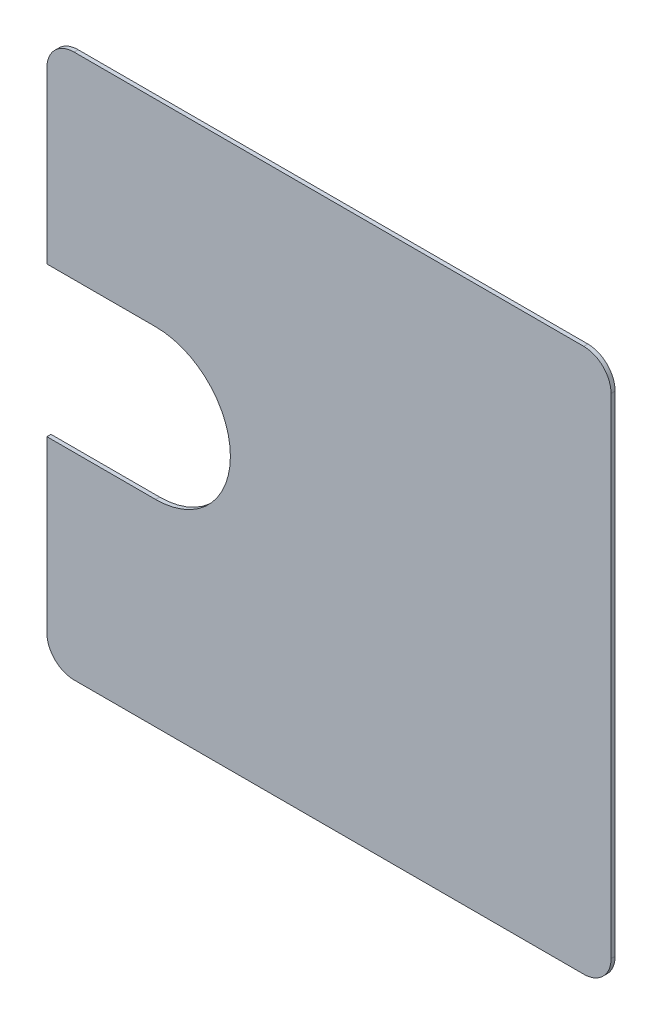
SolidWorks part; units mm, degrees
ref_plane "前视基准面" through (0, 0, 0) normal (0, 0, 1) x (1, 0, 0)
ref_plane "上视基准面" through (0, 0, 0) normal (0, 1, 0) x (1, 0, 0)
ref_plane "右视基准面" through (0, 0, 0) normal (1, 0, 0) x (0, 0, -1)
other "Configuration Table"
sketch "草图1" plane through (0, 0, 0) normal (0, 0, 1) x (1, 0, 0)
  line L0 (-127.5, 55) -> (-207.5, 55)
  line L1 (-187.5, -200) -> (187.5, -200)
  line L2 (-207.5, -180) -> (-207.5, -55)
  line L3 (-187.5, 200) -> (187.5, 200)
  line L4 (207.5, -180) -> (207.5, 180)
  line L5 (-207.5, -200) -> (207.5, 200) construction
  line L6 (-207.5, 200) -> (207.5, -200) construction
  line L7 (-127.5, -55) -> (-207.5, -55)
  line L8 (-207.5, 55) -> (-207.5, 180)
  line L9 (0, 0) -> (-50000, 0) construction
  arc A0 (-127.5, -55) -> (-127.5, 55) centre (-127.5, 0) ccw
  arc A1 (187.5, -200) -> (207.5, -180) centre (187.5, -180) ccw
  arc A2 (-187.5, -200) -> (-207.5, -180) centre (-187.5, -180) cw
  arc A3 (-207.5, 180) -> (-187.5, 200) centre (-187.5, 180) cw
  arc A4 (187.5, 200) -> (207.5, 180) centre (187.5, 180) cw
  point P0 (0, 0)
  dimension "D3" = 110
  dimension "D4" = 20
  dimension "D1" = 415
  dimension "D2" = 400
  dimension "D5" = 80
extrude "凸台-拉伸1" add sketch "草图1" along normal blind 3
